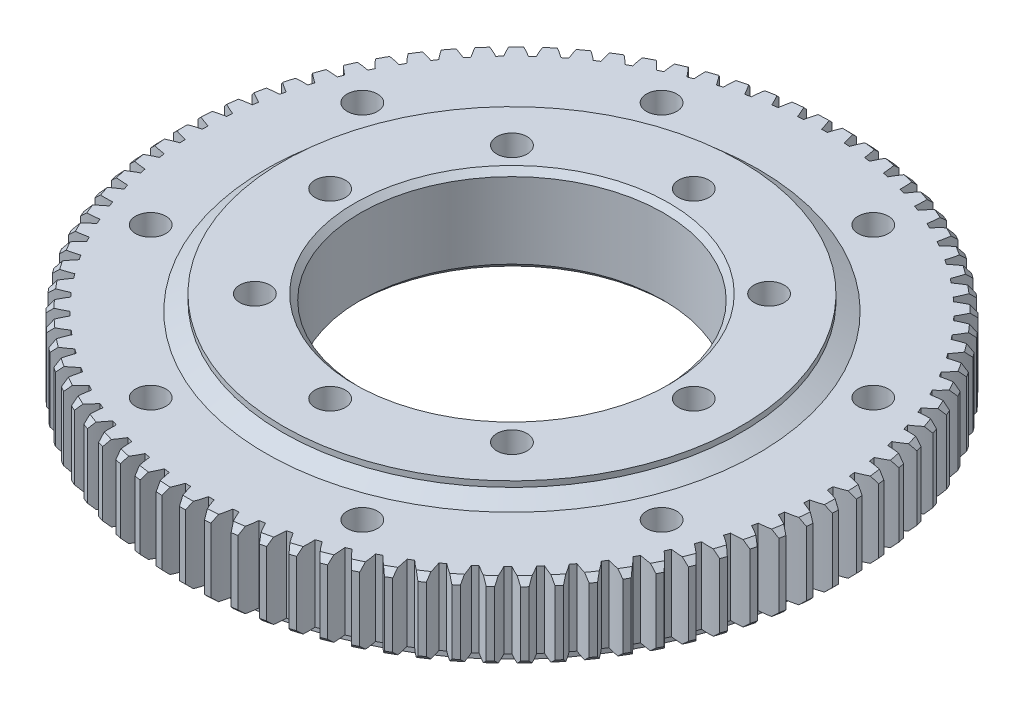
SolidWorks part; units mm, degrees
ref_plane "前视基准面" through (0, 0, 0) normal (0, 0, 1) x (1, 0, 0)
ref_plane "上视基准面" through (0, 0, 0) normal (0, 1, 0) x (1, 0, 0)
ref_plane "右视基准面" through (0, 0, 0) normal (1, 0, 0) x (0, 0, -1)
sketch "草图2" plane through (0, 0, 0) normal (1, 0, 0) x (0, 0, -1)
  line L0 (0, 0) -> (0, 460505.6577) construction
  line L1 (-60.5, 13.5) -> (-60.5, 12)
  line L2 (-58.2899, -4.6985) -> (-58.2899, -9.5)
  line L3 (-58.2899, -9.5) -> (-40, -9.5)
  line L4 (-40, -9.5) -> (-40, 13.5)
  line L5 (-40, 13.5) -> (-60.5, 13.5)
  line L6 (-61.7101, 9.5) -> (-61.7101, 4.6985)
  line L7 (-59.5, -4.9749) -> (-59.5, -10.5)
  line L8 (-59.5, -13.5) -> (-80, -13.5)
  line L9 (-80, -13.5) -> (-80, -10.5)
  line L10 (-80, -10.5) -> (-87, -10.5)
  line L11 (-87, -10.5) -> (-87, 9.5)
  line L12 (-87, 9.5) -> (-61.7101, 9.5)
  line L13 (-61.7101, 4.6985) -> (-58.2899, -4.6985) construction
  line L14 (-60.5, 12) -> (-58, 12)
  line L15 (-58, 12) -> (-58, 10.5)
  line L16 (-58, 10.5) -> (-60.5, 10.5)
  line L17 (-60.5, 10.5) -> (-60.5, 4.9749)
  line L18 (-59.5, -10.5) -> (-62, -10.5)
  line L19 (-62, -10.5) -> (-62, -12)
  line L20 (-62, -12) -> (-59.5, -12)
  line L21 (-59.5, -12) -> (-59.5, -13.5)
  arc A0 (-60.5, 4.9749) -> (-58.2899, -4.6985) centre (-60, 0) cw
  arc A1 (-61.7101, 4.6985) -> (-59.5, -4.9749) centre (-60, 0) ccw
  point P15 (-60, 0)
  dimension "D1" = 23
  dimension "D5" = 119
  dimension "D11" = 5
  dimension "D2" = 80
  dimension "D3" = 120
  dimension "D4" = 121
  dimension "D6" = 23
  dimension "D7" = 4
  dimension "D8" = 174
  dimension "D9" = 160
  dimension "D10" = 20
  dimension "D12" = 1.2101
  dimension "D13" = 1.5
  dimension "D14" = 1.5
  dimension "D15" = 2.5
revolve "旋转1" add sketch "草图2" angle 360 about L0
sketch "草图3" plane through (0, 0, 0) normal (1, 0, 0) x (0, 0, -1)
  line L0 (-60, 5) -> (-60, -5)
  arc A0 (-60, 5) -> (-60, -5) centre (-60, 0) ccw
  dimension "D1" = 60
  dimension "D2" = 5
revolve "旋转2" add sketch "草图3" angle 360 about L0
pattern_circular "阵列(圆周)2" count 30 over 360 about axis through (0, 9.5, 0) along (0, -1, 0) of bodies 103
chamfer "倒角1" distance 1.5 angle 45 2 edges at (0, -10.5, -87) (0, 9.5, -87)
sketch "草图4" plane through (0, 9.5, 0) normal (0, 1, 0) x (1, 0, 0)
  line L0 (0, 0) -> (0, 87) construction
  line L1 (0, 0) -> (29.7558, 81.7533) construction
  line L2 (0, 85) -> (27.3185, 75.0569) construction
  line L3 (0, 0) -> (27.3185, 75.0569) construction
  line L4 (0, 0) -> (28.7023, 74.5387) construction
  circle A0 centre (0, 0) radius 87 construction
  arc A1 (2.4208, 86.9663) -> (-2.4208, 86.9663) centre (0, 0) ccw
  circle A2 centre (0, 0) radius 85 construction
  arc A3 (0.741, 82.4967) -> (-0.7853, 82.4963) centre (0, 0) ccw
  arc A5 (0.8116, 86.9962) -> (-0.7853, 82.4963) centre (27.3185, 75.0569) ccw construction
  arc A6 (-2.4208, 86.9663) -> (-0.741, 82.4967) centre (-28.7023, 74.5387) cw
  arc A7 (2.4208, 86.9663) -> (0.741, 82.4967) centre (28.7023, 74.5387) ccw
  circle M10 centre (0, 0) radius 85.5
  dimension "D2" = 170
  dimension "D3" = 165
  dimension "D4" = 2
  dimension "D1" = 20
  dimension "D5" = 1.06
extrude "切除-拉伸1" cut sketch "草图4" against normal through all contours A7 A6 A3 M10 | A7 A1 A6 M10 region at (0, 9.5, -86.2804) region at (0, 9.5, -84.2062)
pattern_circular "阵列(圆周)3" count 85 over 360 about axis through (0, 9.5, 0) along (0, 1, 0) of "切除-拉伸1"
sketch "草图5" plane through (0, 13.5, 0) normal (0, 1, 0) x (1, 0, 0)
  circle A0 centre (0, 0) radius 48 construction
  circle A1 centre (0, 48) radius 4
  dimension "D1" = 96
  dimension "D2" = 8
extrude "切除-拉伸2" cut sketch "草图5" against normal through all
pattern_circular "阵列(圆周)4" count 8 over 360 about axis through (0, 13.5, 0) along (0, -1, 0) of "切除-拉伸2"
sketch "草图6" plane through (0, 9.5, 0) normal (0, 1, 0) x (1, 0, 0)
  line L0 (-27.9359, 67.4432) -> (0, 0) construction
  line L1 (0, 0) -> (0, 73) construction
  circle A0 centre (0, 0) radius 73 construction
  circle A1 centre (-27.9359, 67.4432) radius 4
  dimension "D1" = 146
  dimension "D2" = 8
  dimension "D3" = 22.5
extrude "切除-拉伸3" cut sketch "草图6" against normal through all
pattern_circular "阵列(圆周)5" count 8 over 360 about axis through (0, 9.5, 0) along (0, -1, 0) of "切除-拉伸3"
sketch "草图7" plane through (0, 0, 0) normal (0, 0, 1) x (1, 0, 0)
  line L0 (-60.5, 12) -> (-58, 12)
  line L1 (-60.5, 12) -> (60.5, 12) construction
  line L2 (-58, 12) -> (-58, 10.5)
  line L3 (58, 10.5) -> (-58, 10.5) construction
  line L4 (-58, 10.5) -> (-60.5, 10.5)
  line L5 (60.5, 10.5) -> (-60.5, 10.5) construction
  line L8 (0, 0) -> (0, 50000) construction
  line L10 (-60.5, 12) -> (-65, 9.5)
  line L11 (-65, 9.5) -> (-60.5, 10.5)
  line L12 (31.9359, 9.5) -> (23.9359, 9.5) construction
  line L13 (-59.5, -10.5) -> (-62, -10.5)
  line L14 (-62, -10.5) -> (62, -10.5) construction
  line L15 (-59.5, -10.5) -> (59.5, -10.5) construction
  line L16 (-62, -10.5) -> (-62, -12)
  line L17 (62, -12) -> (-62, -12) construction
  line L18 (-62, -12) -> (-59.5, -12)
  line L19 (59.5, -12) -> (-59.5, -12) construction
  line L20 (-59.5, -12) -> (-55, -9.5)
  line L21 (-58.2899, -9.5) -> (58.2899, -9.5) construction
  line L22 (-55, -9.5) -> (-59.5, -10.5)
  dimension "D1" = 7
  dimension "D2" = 7
revolve "旋转3" add sketch "草图7" angle 360 about L8
chamfer "倒角2" distance 1.5 angle 45 2 edges at (0, -9.5, -40) (0, 13.5, -40)
